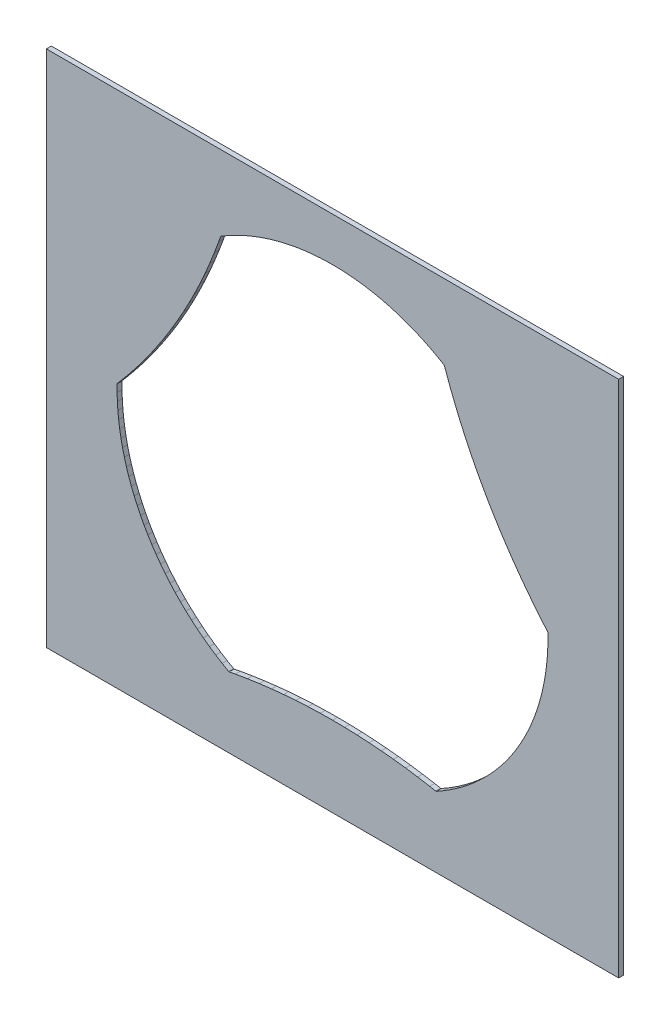
SolidWorks part; units mm, degrees
ref_plane "Front Plane" through (0, 0, 0) normal (0, 0, 1) x (1, 0, 0)
ref_plane "Top Plane" through (0, 0, 0) normal (0, 1, 0) x (1, 0, 0)
ref_plane "Right Plane" through (0, 0, 0) normal (1, 0, 0) x (0, 0, -1)
sketch "Model" plane through (0, 0, 0) normal (0, 0, 1) x (1, 0, 0)
  line L0 (125.677, -154.6098) -> (127.2049, -154.7174)
  line L1 (127.2049, -154.7174) -> (128.7281, -154.8785)
  line L2 (128.7281, -154.8785) -> (130.2447, -155.093)
  line L3 (130.2447, -155.093) -> (131.7528, -155.3606)
  line L4 (131.7528, -155.3606) -> (133.2506, -155.681)
  line L5 (133.2506, -155.681) -> (134.7362, -156.0539)
  line L6 (134.7362, -156.0539) -> (136.2078, -156.4787)
  line L7 (136.2078, -156.4787) -> (137.6636, -156.9549)
  line L8 (137.6636, -156.9549) -> (139.1018, -157.4819)
  line L9 (139.1018, -157.4819) -> (140.5205, -158.0591)
  line L10 (140.5205, -158.0591) -> (141.9181, -158.6858)
  line L11 (141.9181, -158.6858) -> (143.2929, -159.3612)
  line L12 (143.2929, -159.3612) -> (144.6431, -160.0844)
  line L13 (144.6431, -160.0844) -> (145.967, -160.8546)
  line L14 (145.967, -160.8546) -> (145.9831, -160.8702)
  line L15 (145.9831, -160.8702) -> (146.0021, -160.8822)
  line L16 (146.0021, -160.8822) -> (146.0122, -160.8983)
  line L17 (146.0122, -160.8983) -> (146.0259, -160.9116)
  line L18 (146.0259, -160.9116) -> (146.0336, -160.9326)
  line L19 (146.0336, -160.9326) -> (146.0455, -160.9517)
  line L20 (146.0455, -160.9517) -> (146.451, -162.1194)
  line L21 (146.451, -162.1194) -> (147.3137, -164.4362)
  line L22 (147.3137, -164.4362) -> (148.2279, -166.7332)
  line L23 (148.2279, -166.7332) -> (149.193, -169.0092)
  line L24 (149.193, -169.0092) -> (150.2086, -171.2632)
  line L25 (150.2086, -171.2632) -> (151.2742, -173.494)
  line L26 (151.2742, -173.494) -> (152.3892, -175.7006)
  line L27 (152.3892, -175.7006) -> (153.5531, -177.8817)
  line L28 (153.5531, -177.8817) -> (154.7653, -180.0363)
  line L29 (154.7653, -180.0363) -> (156.0251, -182.1634)
  line L30 (156.0251, -182.1634) -> (157.3321, -184.2619)
  line L31 (157.3321, -184.2619) -> (158.6855, -186.3308)
  line L32 (158.6855, -186.3308) -> (160.0847, -188.369)
  line L33 (160.0847, -188.369) -> (161.5289, -190.3755)
  line L34 (161.5289, -190.3755) -> (163.0174, -192.3494)
  line L35 (163.0174, -192.3494) -> (164.5496, -194.2896)
  line L36 (164.5496, -194.2896) -> (166.1246, -196.1952)
  line L37 (166.1246, -196.1952) -> (166.9332, -197.1302)
  line L38 (166.9332, -197.1302) -> (166.9437, -197.15)
  line L39 (166.9437, -197.15) -> (166.9581, -197.1673)
  line L40 (166.9581, -197.1673) -> (166.9627, -197.1857)
  line L41 (166.9627, -197.1857) -> (166.9716, -197.2025)
  line L42 (166.9716, -197.2025) -> (166.9725, -197.2249)
  line L43 (166.9725, -197.2249) -> (166.9779, -197.2467)
  line L44 (166.9779, -197.2467) -> (166.983, -198.7784)
  line L45 (166.983, -198.7784) -> (166.9343, -200.3093)
  line L46 (166.9343, -200.3093) -> (166.8318, -201.8375)
  line L47 (166.8318, -201.8375) -> (166.6757, -203.3612)
  line L48 (166.6757, -203.3612) -> (166.4662, -204.8785)
  line L49 (166.4662, -204.8785) -> (166.2036, -206.3875)
  line L50 (166.2036, -206.3875) -> (165.8881, -207.8864)
  line L51 (165.8881, -207.8864) -> (165.5201, -209.3732)
  line L52 (165.5201, -209.3732) -> (165.1002, -210.8462)
  line L53 (165.1002, -210.8462) -> (164.6288, -212.3036)
  line L54 (164.6288, -212.3036) -> (164.1065, -213.7435)
  line L55 (164.1065, -213.7435) -> (163.534, -215.1641)
  line L56 (163.534, -215.1641) -> (162.9119, -216.5638)
  line L57 (162.9119, -216.5638) -> (162.2411, -217.9408)
  line L58 (162.2411, -217.9408) -> (161.5223, -219.2933)
  line L59 (161.5223, -219.2933) -> (160.7565, -220.6198)
  line L60 (160.7565, -220.6198) -> (159.9445, -221.9186)
  line L61 (159.9445, -221.9186) -> (159.0874, -223.188)
  line L62 (159.0874, -223.188) -> (158.1863, -224.4266)
  line L63 (158.1863, -224.4266) -> (157.2423, -225.6327)
  line L64 (157.2423, -225.6327) -> (156.2564, -226.805)
  line L65 (156.2564, -226.805) -> (155.23, -227.9419)
  line L66 (155.23, -227.9419) -> (154.1643, -229.0421)
  line L67 (154.1643, -229.0421) -> (153.0607, -230.1041)
  line L68 (153.0607, -230.1041) -> (151.9204, -231.1268)
  line L69 (151.9204, -231.1268) -> (150.7449, -232.1087)
  line L70 (150.7449, -232.1087) -> (149.5356, -233.0488)
  line L71 (149.5356, -233.0488) -> (148.2941, -233.9458)
  line L72 (148.2941, -233.9458) -> (147.0218, -234.7987)
  line L73 (147.0218, -234.7987) -> (145.7204, -235.6064)
  line L74 (145.7204, -235.6064) -> (144.3914, -236.3678)
  line L75 (144.3914, -236.3678) -> (144.3698, -236.374)
  line L76 (144.3698, -236.374) -> (144.3499, -236.3845)
  line L77 (144.3499, -236.3845) -> (144.3309, -236.3851)
  line L78 (144.3309, -236.3851) -> (144.3126, -236.3903)
  line L79 (144.3126, -236.3903) -> (144.2905, -236.3865)
  line L80 (144.2905, -236.3865) -> (144.2681, -236.3873)
  line L81 (144.2681, -236.3873) -> (143.054, -236.1546)
  line L82 (143.054, -236.1546) -> (140.6163, -235.7434)
  line L83 (140.6163, -235.7434) -> (138.1699, -235.3866)
  line L84 (138.1699, -235.3866) -> (135.7162, -235.0844)
  line L85 (135.7162, -235.0844) -> (133.2564, -234.8369)
  line L86 (133.2564, -234.8369) -> (130.7917, -234.6443)
  line L87 (130.7917, -234.6443) -> (128.3233, -234.5067)
  line L88 (128.3233, -234.5067) -> (125.8525, -234.4241)
  line L89 (125.8525, -234.4241) -> (123.3804, -234.3965)
  line L90 (123.3804, -234.3965) -> (120.9083, -234.4241)
  line L91 (120.9083, -234.4241) -> (118.4375, -234.5067)
  line L92 (118.4375, -234.5067) -> (115.9691, -234.6443)
  line L93 (115.9691, -234.6443) -> (113.5044, -234.8369)
  line L94 (113.5044, -234.8369) -> (111.0446, -235.0844)
  line L95 (111.0446, -235.0844) -> (108.5909, -235.3866)
  line L96 (108.5909, -235.3866) -> (106.1445, -235.7434)
  line L97 (106.1445, -235.7434) -> (103.7067, -236.1546)
  line L98 (103.7067, -236.1546) -> (102.4927, -236.3873)
  line L99 (102.4927, -236.3873) -> (102.4703, -236.3865)
  line L100 (102.4703, -236.3865) -> (102.4482, -236.3903)
  line L101 (102.4482, -236.3903) -> (102.4299, -236.3851)
  line L102 (102.4299, -236.3851) -> (102.4109, -236.3845)
  line L103 (102.4109, -236.3845) -> (102.391, -236.374)
  line L104 (102.391, -236.374) -> (102.3694, -236.3678)
  line L105 (102.3694, -236.3678) -> (101.0404, -235.6064)
  line L106 (101.0404, -235.6064) -> (99.739, -234.7987)
  line L107 (99.739, -234.7987) -> (98.4667, -233.9458)
  line L108 (98.4667, -233.9458) -> (97.2252, -233.0488)
  line L109 (97.2252, -233.0488) -> (96.0159, -232.1087)
  line L110 (96.0159, -232.1087) -> (94.8404, -231.1268)
  line L111 (94.8404, -231.1268) -> (93.7001, -230.1041)
  line L112 (93.7001, -230.1041) -> (92.5965, -229.0421)
  line L113 (92.5965, -229.0421) -> (91.5308, -227.9419)
  line L114 (91.5308, -227.9419) -> (90.5044, -226.805)
  line L115 (90.5044, -226.805) -> (89.5185, -225.6327)
  line L116 (89.5185, -225.6327) -> (88.5745, -224.4266)
  line L117 (88.5745, -224.4266) -> (87.6733, -223.188)
  line L118 (87.6733, -223.188) -> (86.8163, -221.9186)
  line L119 (86.8163, -221.9186) -> (86.0043, -220.6198)
  line L120 (86.0043, -220.6198) -> (85.2385, -219.2933)
  line L121 (85.2385, -219.2933) -> (84.5197, -217.9408)
  line L122 (84.5197, -217.9408) -> (83.8488, -216.5638)
  line L123 (83.8488, -216.5638) -> (83.2268, -215.1641)
  line L124 (83.2268, -215.1641) -> (82.6542, -213.7435)
  line L125 (82.6542, -213.7435) -> (82.132, -212.3036)
  line L126 (82.132, -212.3036) -> (81.6606, -210.8462)
  line L127 (81.6606, -210.8462) -> (81.2406, -209.3732)
  line L128 (81.2406, -209.3732) -> (80.8727, -207.8864)
  line L129 (80.8727, -207.8864) -> (80.5572, -206.3875)
  line L130 (80.5572, -206.3875) -> (80.2946, -204.8785)
  line L131 (80.2946, -204.8785) -> (80.0851, -203.3612)
  line L132 (80.0851, -203.3612) -> (79.929, -201.8375)
  line L133 (79.929, -201.8375) -> (79.8265, -200.3093)
  line L134 (79.8265, -200.3093) -> (79.7778, -198.7784)
  line L135 (79.7778, -198.7784) -> (79.7828, -197.2467)
  line L136 (79.7828, -197.2467) -> (79.7883, -197.2249)
  line L137 (79.7883, -197.2249) -> (79.7892, -197.2025)
  line L138 (79.7892, -197.2025) -> (79.7981, -197.1857)
  line L139 (79.7981, -197.1857) -> (79.8027, -197.1672)
  line L140 (79.8027, -197.1672) -> (79.8171, -197.15)
  line L141 (79.8171, -197.15) -> (79.8276, -197.1302)
  line L142 (79.8276, -197.1302) -> (80.6361, -196.1952)
  line L143 (80.6361, -196.1952) -> (82.2112, -194.2896)
  line L144 (82.2112, -194.2896) -> (83.7433, -192.3494)
  line L145 (83.7433, -192.3494) -> (85.2319, -190.3755)
  line L146 (85.2319, -190.3755) -> (86.6761, -188.369)
  line L147 (86.6761, -188.369) -> (88.0753, -186.3308)
  line L148 (88.0753, -186.3308) -> (89.4287, -184.2619)
  line L149 (89.4287, -184.2619) -> (90.7356, -182.1634)
  line L150 (90.7356, -182.1634) -> (91.9955, -180.0363)
  line L151 (91.9955, -180.0363) -> (93.2077, -177.8817)
  line L152 (93.2077, -177.8817) -> (94.3716, -175.7005)
  line L153 (94.3716, -175.7005) -> (95.4866, -173.494)
  line L154 (95.4866, -173.494) -> (96.5521, -171.2632)
  line L155 (96.5521, -171.2632) -> (97.5677, -169.0092)
  line L156 (97.5677, -169.0092) -> (98.5329, -166.7332)
  line L157 (98.5329, -166.7332) -> (99.447, -164.4362)
  line L158 (99.447, -164.4362) -> (100.3098, -162.1194)
  line L159 (100.3098, -162.1194) -> (100.7153, -160.9517)
  line L160 (100.7153, -160.9517) -> (100.7272, -160.9326)
  line L161 (100.7272, -160.9326) -> (100.7349, -160.9116)
  line L162 (100.7349, -160.9116) -> (100.7486, -160.8983)
  line L163 (100.7486, -160.8983) -> (100.7587, -160.8822)
  line L164 (100.7587, -160.8822) -> (100.7776, -160.8702)
  line L165 (100.7776, -160.8702) -> (100.7938, -160.8546)
  line L166 (100.7938, -160.8546) -> (102.1177, -160.0844)
  line L167 (102.1177, -160.0844) -> (103.4679, -159.3612)
  line L168 (103.4679, -159.3612) -> (104.8426, -158.6858)
  line L169 (104.8426, -158.6858) -> (106.2403, -158.0591)
  line L170 (106.2403, -158.0591) -> (107.659, -157.4819)
  line L171 (107.659, -157.4819) -> (109.0972, -156.9549)
  line L172 (109.0972, -156.9549) -> (110.553, -156.4787)
  line L173 (110.553, -156.4787) -> (112.0246, -156.0539)
  line L174 (112.0246, -156.0539) -> (113.5102, -155.681)
  line L175 (113.5102, -155.681) -> (115.008, -155.3606)
  line L176 (115.008, -155.3606) -> (116.5161, -155.093)
  line L177 (116.5161, -155.093) -> (118.0327, -154.8785)
  line L178 (118.0327, -154.8785) -> (119.5559, -154.7174)
  line L179 (119.5559, -154.7174) -> (121.0838, -154.6098)
  line L180 (121.0838, -154.6098) -> (122.6145, -154.556)
  line L181 (122.6145, -154.556) -> (124.1462, -154.556)
  line L182 (124.1462, -154.556) -> (125.677, -154.6098)
  line L183 (79.7981, -197.1857) -> (166.9627, -197.1857) construction
  line L184 (144.3309, -236.3851) -> (100.7486, -160.8983) construction
  line L185 (146.0122, -160.8983) -> (102.4299, -236.3851) construction
  line L186 (123.3804, -197.1857) -> (123.3804, -200.0978) construction
  line L187 (122.5397, -198.6417) -> (125.0617, -197.1857) construction
  line L188 (124.221, -198.6417) -> (121.6991, -197.1857) construction
  point P190 (123.3804, -198.1564)
sketch "Sketch2" plane through (0, 0, 0) normal (0, 0, 1) x (1, 0, 0)
  line L1 (65.4557, -250.6328) -> (181.3051, -250.6328)
  line L2 (65.4557, -250.6328) -> (65.4557, -145.68)
  line L3 (65.4557, -145.68) -> (181.3051, -145.68)
  line L4 (181.3051, -250.6328) -> (181.3051, -145.68)
  line L5 (65.4557, -250.6328) -> (181.3051, -145.68) construction
  line L6 (65.4557, -145.68) -> (181.3051, -250.6328) construction
  point P0 (123.3804, -198.1564)
  dimension "D1" = 104.9528
  dimension "D2" = 115.8494
sketch "Sketch3" plane through (0, 0, 0) normal (0, 0, 1) x (1, 0, 0)
  line L0 (80.6361, -196.1952) -> (82.2112, -194.2896) construction
  line L1 (79.8276, -197.1302) -> (80.6361, -196.1952) construction
  line L2 (79.8171, -197.15) -> (79.8276, -197.1302) construction
  line L3 (79.8027, -197.1672) -> (79.8171, -197.15) construction
  line L4 (79.7981, -197.1857) -> (79.8027, -197.1672) construction
  line L5 (79.7892, -197.2025) -> (79.7981, -197.1857) construction
  line L6 (79.7883, -197.2249) -> (79.7892, -197.2025) construction
  line L7 (79.7828, -197.2467) -> (79.7883, -197.2249) construction
  line L8 (79.7778, -198.7784) -> (79.7828, -197.2467) construction
  line L9 (79.8265, -200.3093) -> (79.7778, -198.7784) construction
  line L10 (79.929, -201.8375) -> (79.8265, -200.3093) construction
  line L11 (80.0851, -203.3612) -> (79.929, -201.8375) construction
  line L12 (80.2946, -204.8785) -> (80.0851, -203.3612) construction
  line L13 (80.5572, -206.3875) -> (80.2946, -204.8785) construction
  line L14 (80.8727, -207.8864) -> (80.5572, -206.3875) construction
  line L15 (81.2406, -209.3732) -> (80.8727, -207.8864) construction
  line L16 (81.6606, -210.8462) -> (81.2406, -209.3732) construction
  line L17 (82.132, -212.3036) -> (81.6606, -210.8462) construction
  line L18 (82.6542, -213.7435) -> (82.132, -212.3036) construction
  line L19 (83.2268, -215.1641) -> (82.6542, -213.7435) construction
  line L20 (83.8488, -216.5638) -> (83.2268, -215.1641) construction
  line L21 (84.5197, -217.9408) -> (83.8488, -216.5638) construction
  line L22 (85.2385, -219.2933) -> (84.5197, -217.9408) construction
  line L23 (86.0043, -220.6198) -> (85.2385, -219.2933) construction
  line L24 (86.8163, -221.9186) -> (86.0043, -220.6198) construction
  line L25 (87.6733, -223.188) -> (86.8163, -221.9186) construction
  line L26 (88.5745, -224.4266) -> (87.6733, -223.188) construction
  line L27 (89.5185, -225.6327) -> (88.5745, -224.4266) construction
  line L28 (90.5044, -226.805) -> (89.5185, -225.6327) construction
  line L29 (91.5308, -227.9419) -> (90.5044, -226.805) construction
  line L30 (92.5965, -229.0421) -> (91.5308, -227.9419) construction
  line L31 (93.7001, -230.1041) -> (92.5965, -229.0421) construction
  line L32 (94.8404, -231.1268) -> (93.7001, -230.1041) construction
  line L33 (96.0159, -232.1087) -> (94.8404, -231.1268) construction
  line L34 (97.2252, -233.0488) -> (96.0159, -232.1087) construction
  line L35 (98.4667, -233.9458) -> (97.2252, -233.0488) construction
  line L36 (99.739, -234.7987) -> (98.4667, -233.9458) construction
  line L37 (101.0404, -235.6064) -> (99.739, -234.7987) construction
  line L38 (102.3694, -236.3678) -> (101.0404, -235.6064) construction
  line L39 (102.391, -236.374) -> (102.3694, -236.3678) construction
  line L40 (102.4109, -236.3845) -> (102.391, -236.374) construction
  line L41 (102.4299, -236.3851) -> (102.4109, -236.3845) construction
  line L42 (102.4482, -236.3903) -> (102.4299, -236.3851) construction
  line L43 (102.4703, -236.3865) -> (102.4482, -236.3903) construction
  line L44 (102.4927, -236.3873) -> (102.4703, -236.3865) construction
  line L45 (103.7067, -236.1546) -> (102.4927, -236.3873) construction
  line L46 (106.1445, -235.7434) -> (103.7067, -236.1546) construction
  line L47 (108.5909, -235.3866) -> (106.1445, -235.7434) construction
  line L48 (111.0446, -235.0844) -> (108.5909, -235.3866) construction
  line L49 (113.5044, -234.8369) -> (111.0446, -235.0844) construction
  line L50 (115.9691, -234.6443) -> (113.5044, -234.8369) construction
  line L51 (118.4375, -234.5067) -> (115.9691, -234.6443) construction
  line L52 (120.9083, -234.4241) -> (118.4375, -234.5067) construction
  line L53 (123.3804, -234.3965) -> (120.9083, -234.4241) construction
  line L54 (125.8525, -234.4241) -> (123.3804, -234.3965) construction
  line L55 (128.3233, -234.5067) -> (125.8525, -234.4241) construction
  line L56 (130.7917, -234.6443) -> (128.3233, -234.5067) construction
  line L57 (133.2564, -234.8369) -> (130.7917, -234.6443) construction
  line L58 (135.7162, -235.0844) -> (133.2564, -234.8369) construction
  line L59 (138.1699, -235.3866) -> (135.7162, -235.0844) construction
  line L60 (140.6163, -235.7434) -> (138.1699, -235.3866) construction
  line L61 (143.054, -236.1546) -> (140.6163, -235.7434) construction
  line L62 (144.2681, -236.3873) -> (143.054, -236.1546) construction
  line L63 (144.2905, -236.3865) -> (144.2681, -236.3873) construction
  line L64 (144.3126, -236.3903) -> (144.2905, -236.3865) construction
  line L65 (144.3309, -236.3851) -> (144.3126, -236.3903) construction
  line L66 (144.3499, -236.3845) -> (144.3309, -236.3851) construction
  line L67 (144.3698, -236.374) -> (144.3499, -236.3845) construction
  line L68 (144.3914, -236.3678) -> (144.3698, -236.374) construction
  line L69 (145.7204, -235.6064) -> (144.3914, -236.3678) construction
  line L70 (147.0218, -234.7987) -> (145.7204, -235.6064) construction
  line L71 (148.2941, -233.9458) -> (147.0218, -234.7987) construction
  line L72 (149.5356, -233.0488) -> (148.2941, -233.9458) construction
  line L73 (150.7449, -232.1087) -> (149.5356, -233.0488) construction
  line L74 (151.9204, -231.1268) -> (150.7449, -232.1087) construction
  line L75 (153.0607, -230.1041) -> (151.9204, -231.1268) construction
  line L76 (154.1643, -229.0421) -> (153.0607, -230.1041) construction
  line L77 (155.23, -227.9419) -> (154.1643, -229.0421) construction
  line L78 (156.2564, -226.805) -> (155.23, -227.9419) construction
  line L79 (157.2423, -225.6327) -> (156.2564, -226.805) construction
  line L80 (158.1863, -224.4266) -> (157.2423, -225.6327) construction
  line L81 (159.0874, -223.188) -> (158.1863, -224.4266) construction
  line L82 (159.9445, -221.9186) -> (159.0874, -223.188) construction
  line L83 (160.7565, -220.6198) -> (159.9445, -221.9186) construction
  line L84 (161.5223, -219.2933) -> (160.7565, -220.6198) construction
  line L85 (162.2411, -217.9408) -> (161.5223, -219.2933) construction
  line L86 (162.9119, -216.5638) -> (162.2411, -217.9408) construction
  line L87 (163.534, -215.1641) -> (162.9119, -216.5638) construction
  line L88 (164.1065, -213.7435) -> (163.534, -215.1641) construction
  line L89 (164.6288, -212.3036) -> (164.1065, -213.7435) construction
  line L90 (165.1002, -210.8462) -> (164.6288, -212.3036) construction
  line L91 (165.5201, -209.3732) -> (165.1002, -210.8462) construction
  line L92 (165.8881, -207.8864) -> (165.5201, -209.3732) construction
  line L93 (166.2036, -206.3875) -> (165.8881, -207.8864) construction
  line L94 (166.4662, -204.8785) -> (166.2036, -206.3875) construction
  line L95 (166.6757, -203.3612) -> (166.4662, -204.8785) construction
  line L96 (166.8318, -201.8375) -> (166.6757, -203.3612) construction
  line L97 (166.9343, -200.3093) -> (166.8318, -201.8375) construction
  line L98 (166.983, -198.7784) -> (166.9343, -200.3093) construction
  line L99 (166.9779, -197.2467) -> (166.983, -198.7784) construction
  line L100 (166.9725, -197.2249) -> (166.9779, -197.2467) construction
  line L101 (166.9716, -197.2025) -> (166.9725, -197.2249) construction
  line L102 (166.9627, -197.1857) -> (166.9716, -197.2025) construction
  line L103 (166.9581, -197.1673) -> (166.9627, -197.1857) construction
  line L104 (166.9437, -197.15) -> (166.9581, -197.1673) construction
  line L105 (166.9332, -197.1302) -> (166.9437, -197.15) construction
  line L106 (166.1246, -196.1952) -> (166.9332, -197.1302) construction
  line L107 (164.5496, -194.2896) -> (166.1246, -196.1952) construction
  line L108 (163.0174, -192.3494) -> (164.5496, -194.2896) construction
  line L109 (161.5289, -190.3755) -> (163.0174, -192.3494) construction
  line L110 (160.0847, -188.369) -> (161.5289, -190.3755) construction
  line L111 (158.6855, -186.3308) -> (160.0847, -188.369) construction
  line L112 (157.3321, -184.2619) -> (158.6855, -186.3308) construction
  line L113 (156.0251, -182.1634) -> (157.3321, -184.2619) construction
  line L114 (154.7653, -180.0363) -> (156.0251, -182.1634) construction
  line L115 (153.5531, -177.8817) -> (154.7653, -180.0363) construction
  line L116 (152.3892, -175.7006) -> (153.5531, -177.8817) construction
  line L117 (151.2742, -173.494) -> (152.3892, -175.7006) construction
  line L118 (150.2086, -171.2632) -> (151.2742, -173.494) construction
  line L119 (149.193, -169.0092) -> (150.2086, -171.2632) construction
  line L120 (148.2279, -166.7332) -> (149.193, -169.0092) construction
  line L121 (147.3137, -164.4362) -> (148.2279, -166.7332) construction
  line L122 (146.451, -162.1194) -> (147.3137, -164.4362) construction
  line L123 (146.0455, -160.9517) -> (146.451, -162.1194) construction
  line L124 (146.0336, -160.9326) -> (146.0455, -160.9517) construction
  line L125 (146.0259, -160.9116) -> (146.0336, -160.9326) construction
  line L126 (146.0122, -160.8983) -> (146.0259, -160.9116) construction
  line L127 (146.0021, -160.8822) -> (146.0122, -160.8983) construction
  line L128 (145.9831, -160.8702) -> (146.0021, -160.8822) construction
  line L129 (145.967, -160.8546) -> (145.9831, -160.8702) construction
  line L130 (144.6431, -160.0844) -> (145.967, -160.8546) construction
  line L131 (143.2929, -159.3612) -> (144.6431, -160.0844) construction
  line L132 (141.9181, -158.6858) -> (143.2929, -159.3612) construction
  line L133 (140.5205, -158.0591) -> (141.9181, -158.6858) construction
  line L134 (139.1018, -157.4819) -> (140.5205, -158.0591) construction
  line L135 (137.6636, -156.9549) -> (139.1018, -157.4819) construction
  line L136 (136.2078, -156.4787) -> (137.6636, -156.9549) construction
  line L137 (134.7362, -156.0539) -> (136.2078, -156.4787) construction
  line L138 (133.2506, -155.681) -> (134.7362, -156.0539) construction
  line L139 (131.7528, -155.3606) -> (133.2506, -155.681) construction
  line L140 (130.2447, -155.093) -> (131.7528, -155.3606) construction
  line L141 (128.7281, -154.8785) -> (130.2447, -155.093) construction
  line L142 (127.2049, -154.7174) -> (128.7281, -154.8785) construction
  line L143 (125.677, -154.6098) -> (127.2049, -154.7174) construction
  line L144 (124.1462, -154.556) -> (125.677, -154.6098) construction
  line L145 (122.6145, -154.556) -> (124.1462, -154.556) construction
  line L146 (121.0838, -154.6098) -> (122.6145, -154.556) construction
  line L147 (119.5559, -154.7174) -> (121.0838, -154.6098) construction
  line L148 (118.0327, -154.8785) -> (119.5559, -154.7174) construction
  line L149 (116.5161, -155.093) -> (118.0327, -154.8785) construction
  line L150 (115.008, -155.3606) -> (116.5161, -155.093) construction
  line L151 (113.5102, -155.681) -> (115.008, -155.3606) construction
  line L152 (112.0246, -156.0539) -> (113.5102, -155.681) construction
  line L153 (110.553, -156.4787) -> (112.0246, -156.0539) construction
  line L154 (109.0972, -156.9549) -> (110.553, -156.4787) construction
  line L155 (107.659, -157.4819) -> (109.0972, -156.9549) construction
  line L156 (106.2403, -158.0591) -> (107.659, -157.4819) construction
  line L157 (104.8426, -158.6858) -> (106.2403, -158.0591) construction
  line L158 (103.4679, -159.3612) -> (104.8426, -158.6858) construction
  line L159 (102.1177, -160.0844) -> (103.4679, -159.3612) construction
  line L160 (100.7938, -160.8546) -> (102.1177, -160.0844) construction
  line L161 (100.7776, -160.8702) -> (100.7938, -160.8546) construction
  line L162 (100.7587, -160.8822) -> (100.7776, -160.8702) construction
  line L163 (100.7486, -160.8983) -> (100.7587, -160.8822) construction
  line L164 (100.7349, -160.9116) -> (100.7486, -160.8983) construction
  line L165 (100.7272, -160.9326) -> (100.7349, -160.9116) construction
  line L166 (100.7153, -160.9517) -> (100.7272, -160.9326) construction
  line L167 (100.3098, -162.1194) -> (100.7153, -160.9517) construction
  line L168 (99.447, -164.4362) -> (100.3098, -162.1194) construction
  line L169 (98.5329, -166.7332) -> (99.447, -164.4362) construction
  line L170 (97.5677, -169.0092) -> (98.5329, -166.7332) construction
  line L171 (96.5521, -171.2632) -> (97.5677, -169.0092) construction
  line L172 (95.4866, -173.494) -> (96.5521, -171.2632) construction
  line L173 (94.3716, -175.7005) -> (95.4866, -173.494) construction
  line L174 (93.2077, -177.8817) -> (94.3716, -175.7005) construction
  line L175 (91.9955, -180.0363) -> (93.2077, -177.8817) construction
  line L176 (90.7356, -182.1634) -> (91.9955, -180.0363) construction
  line L177 (89.4287, -184.2619) -> (90.7356, -182.1634) construction
  line L178 (88.0753, -186.3308) -> (89.4287, -184.2619) construction
  line L179 (86.6761, -188.369) -> (88.0753, -186.3308) construction
  line L180 (85.2319, -190.3755) -> (86.6761, -188.369) construction
  line L181 (83.7433, -192.3494) -> (85.2319, -190.3755) construction
  line L182 (82.2112, -194.2896) -> (83.7433, -192.3494) construction
  line L183 (80.6361, -196.1952) -> (82.2112, -194.2896)
  line L184 (79.8276, -197.1302) -> (80.6361, -196.1952)
  line L185 (79.8171, -197.15) -> (79.8276, -197.1302)
  line L186 (79.8027, -197.1672) -> (79.8171, -197.15)
  line L187 (79.7981, -197.1857) -> (79.8027, -197.1672)
  line L188 (79.7892, -197.2025) -> (79.7981, -197.1857)
  line L189 (79.7883, -197.2249) -> (79.7892, -197.2025)
  line L190 (79.7828, -197.2467) -> (79.7883, -197.2249)
  line L191 (79.7778, -198.7784) -> (79.7828, -197.2467)
  line L192 (79.8265, -200.3093) -> (79.7778, -198.7784)
  line L193 (79.929, -201.8375) -> (79.8265, -200.3093)
  line L194 (80.0851, -203.3612) -> (79.929, -201.8375)
  line L195 (80.2946, -204.8785) -> (80.0851, -203.3612)
  line L196 (80.5572, -206.3875) -> (80.2946, -204.8785)
  line L197 (80.8727, -207.8864) -> (80.5572, -206.3875)
  line L198 (81.2406, -209.3732) -> (80.8727, -207.8864)
  line L199 (81.6606, -210.8462) -> (81.2406, -209.3732)
  line L200 (82.132, -212.3036) -> (81.6606, -210.8462)
  line L201 (82.6542, -213.7435) -> (82.132, -212.3036)
  line L202 (83.2268, -215.1641) -> (82.6542, -213.7435)
  line L203 (83.8488, -216.5638) -> (83.2268, -215.1641)
  line L204 (84.5197, -217.9408) -> (83.8488, -216.5638)
  line L205 (85.2385, -219.2933) -> (84.5197, -217.9408)
  line L206 (86.0043, -220.6198) -> (85.2385, -219.2933)
  line L207 (86.8163, -221.9186) -> (86.0043, -220.6198)
  line L208 (87.6733, -223.188) -> (86.8163, -221.9186)
  line L209 (88.5745, -224.4266) -> (87.6733, -223.188)
  line L210 (89.5185, -225.6327) -> (88.5745, -224.4266)
  line L211 (90.5044, -226.805) -> (89.5185, -225.6327)
  line L212 (91.5308, -227.9419) -> (90.5044, -226.805)
  line L213 (92.5965, -229.0421) -> (91.5308, -227.9419)
  line L214 (93.7001, -230.1041) -> (92.5965, -229.0421)
  line L215 (94.8404, -231.1268) -> (93.7001, -230.1041)
  line L216 (96.0159, -232.1087) -> (94.8404, -231.1268)
  line L217 (97.2252, -233.0488) -> (96.0159, -232.1087)
  line L218 (98.4667, -233.9458) -> (97.2252, -233.0488)
  line L219 (99.739, -234.7987) -> (98.4667, -233.9458)
  line L220 (101.0404, -235.6064) -> (99.739, -234.7987)
  line L221 (102.3694, -236.3678) -> (101.0404, -235.6064)
  line L222 (102.391, -236.374) -> (102.3694, -236.3678)
  line L223 (102.4109, -236.3845) -> (102.391, -236.374)
  line L224 (102.4299, -236.3851) -> (102.4109, -236.3845)
  line L225 (102.4482, -236.3903) -> (102.4299, -236.3851)
  line L226 (102.4703, -236.3865) -> (102.4482, -236.3903)
  line L227 (102.4927, -236.3873) -> (102.4703, -236.3865)
  line L228 (103.7067, -236.1546) -> (102.4927, -236.3873)
  line L229 (106.1445, -235.7434) -> (103.7067, -236.1546)
  line L230 (108.5909, -235.3866) -> (106.1445, -235.7434)
  line L231 (111.0446, -235.0844) -> (108.5909, -235.3866)
  line L232 (113.5044, -234.8369) -> (111.0446, -235.0844)
  line L233 (115.9691, -234.6443) -> (113.5044, -234.8369)
  line L234 (118.4375, -234.5067) -> (115.9691, -234.6443)
  line L235 (120.9083, -234.4241) -> (118.4375, -234.5067)
  line L236 (123.3804, -234.3965) -> (120.9083, -234.4241)
  line L237 (125.8525, -234.4241) -> (123.3804, -234.3965)
  line L238 (128.3233, -234.5067) -> (125.8525, -234.4241)
  line L239 (130.7917, -234.6443) -> (128.3233, -234.5067)
  line L240 (133.2564, -234.8369) -> (130.7917, -234.6443)
  line L241 (135.7162, -235.0844) -> (133.2564, -234.8369)
  line L242 (138.1699, -235.3866) -> (135.7162, -235.0844)
  line L243 (140.6163, -235.7434) -> (138.1699, -235.3866)
  line L244 (143.054, -236.1546) -> (140.6163, -235.7434)
  line L245 (144.2681, -236.3873) -> (143.054, -236.1546)
  line L246 (144.2905, -236.3865) -> (144.2681, -236.3873)
  line L247 (144.3126, -236.3903) -> (144.2905, -236.3865)
  line L248 (144.3309, -236.3851) -> (144.3126, -236.3903)
  line L249 (144.3499, -236.3845) -> (144.3309, -236.3851)
  line L250 (144.3698, -236.374) -> (144.3499, -236.3845)
  line L251 (144.3914, -236.3678) -> (144.3698, -236.374)
  line L252 (145.7204, -235.6064) -> (144.3914, -236.3678)
  line L253 (147.0218, -234.7987) -> (145.7204, -235.6064)
  line L254 (148.2941, -233.9458) -> (147.0218, -234.7987)
  line L255 (149.5356, -233.0488) -> (148.2941, -233.9458)
  line L256 (150.7449, -232.1087) -> (149.5356, -233.0488)
  line L257 (151.9204, -231.1268) -> (150.7449, -232.1087)
  line L258 (153.0607, -230.1041) -> (151.9204, -231.1268)
  line L259 (154.1643, -229.0421) -> (153.0607, -230.1041)
  line L260 (155.23, -227.9419) -> (154.1643, -229.0421)
  line L261 (156.2564, -226.805) -> (155.23, -227.9419)
  line L262 (157.2423, -225.6327) -> (156.2564, -226.805)
  line L263 (158.1863, -224.4266) -> (157.2423, -225.6327)
  line L264 (159.0874, -223.188) -> (158.1863, -224.4266)
  line L265 (159.9445, -221.9186) -> (159.0874, -223.188)
  line L266 (160.7565, -220.6198) -> (159.9445, -221.9186)
  line L267 (161.5223, -219.2933) -> (160.7565, -220.6198)
  line L268 (162.2411, -217.9408) -> (161.5223, -219.2933)
  line L269 (162.9119, -216.5638) -> (162.2411, -217.9408)
  line L270 (163.534, -215.1641) -> (162.9119, -216.5638)
  line L271 (164.1065, -213.7435) -> (163.534, -215.1641)
  line L272 (164.6288, -212.3036) -> (164.1065, -213.7435)
  line L273 (165.1002, -210.8462) -> (164.6288, -212.3036)
  line L274 (165.5201, -209.3732) -> (165.1002, -210.8462)
  line L275 (165.8881, -207.8864) -> (165.5201, -209.3732)
  line L276 (166.2036, -206.3875) -> (165.8881, -207.8864)
  line L277 (166.4662, -204.8785) -> (166.2036, -206.3875)
  line L278 (166.6757, -203.3612) -> (166.4662, -204.8785)
  line L279 (166.8318, -201.8375) -> (166.6757, -203.3612)
  line L280 (166.9343, -200.3093) -> (166.8318, -201.8375)
  line L281 (166.983, -198.7784) -> (166.9343, -200.3093)
  line L282 (166.9779, -197.2467) -> (166.983, -198.7784)
  line L283 (166.9725, -197.2249) -> (166.9779, -197.2467)
  line L284 (166.9716, -197.2025) -> (166.9725, -197.2249)
  line L285 (166.9627, -197.1857) -> (166.9716, -197.2025)
  line L286 (166.9581, -197.1673) -> (166.9627, -197.1857)
  line L287 (166.9437, -197.15) -> (166.9581, -197.1673)
  line L288 (166.9332, -197.1302) -> (166.9437, -197.15)
  line L289 (166.1246, -196.1952) -> (166.9332, -197.1302)
  line L290 (164.5496, -194.2896) -> (166.1246, -196.1952)
  line L291 (163.0174, -192.3494) -> (164.5496, -194.2896)
  line L292 (161.5289, -190.3755) -> (163.0174, -192.3494)
  line L293 (160.0847, -188.369) -> (161.5289, -190.3755)
  line L294 (158.6855, -186.3308) -> (160.0847, -188.369)
  line L295 (157.3321, -184.2619) -> (158.6855, -186.3308)
  line L296 (156.0251, -182.1634) -> (157.3321, -184.2619)
  line L297 (154.7653, -180.0363) -> (156.0251, -182.1634)
  line L298 (153.5531, -177.8817) -> (154.7653, -180.0363)
  line L299 (152.3892, -175.7006) -> (153.5531, -177.8817)
  line L300 (151.2742, -173.494) -> (152.3892, -175.7006)
  line L301 (150.2086, -171.2632) -> (151.2742, -173.494)
  line L302 (149.193, -169.0092) -> (150.2086, -171.2632)
  line L303 (148.2279, -166.7332) -> (149.193, -169.0092)
  line L304 (147.3137, -164.4362) -> (148.2279, -166.7332)
  line L305 (146.451, -162.1194) -> (147.3137, -164.4362)
  line L306 (146.0455, -160.9517) -> (146.451, -162.1194)
  line L307 (146.0336, -160.9326) -> (146.0455, -160.9517)
  line L308 (146.0259, -160.9116) -> (146.0336, -160.9326)
  line L309 (146.0122, -160.8983) -> (146.0259, -160.9116)
  line L310 (146.0021, -160.8822) -> (146.0122, -160.8983)
  line L311 (145.9831, -160.8702) -> (146.0021, -160.8822)
  line L312 (145.967, -160.8546) -> (145.9831, -160.8702)
  line L313 (144.6431, -160.0844) -> (145.967, -160.8546)
  line L314 (143.2929, -159.3612) -> (144.6431, -160.0844)
  line L315 (141.9181, -158.6858) -> (143.2929, -159.3612)
  line L316 (140.5205, -158.0591) -> (141.9181, -158.6858)
  line L317 (139.1018, -157.4819) -> (140.5205, -158.0591)
  line L318 (137.6636, -156.9549) -> (139.1018, -157.4819)
  line L319 (136.2078, -156.4787) -> (137.6636, -156.9549)
  line L320 (134.7362, -156.0539) -> (136.2078, -156.4787)
  line L321 (133.2506, -155.681) -> (134.7362, -156.0539)
  line L322 (131.7528, -155.3606) -> (133.2506, -155.681)
  line L323 (130.2447, -155.093) -> (131.7528, -155.3606)
  line L324 (128.7281, -154.8785) -> (130.2447, -155.093)
  line L325 (127.2049, -154.7174) -> (128.7281, -154.8785)
  line L326 (125.677, -154.6098) -> (127.2049, -154.7174)
  line L327 (124.1462, -154.556) -> (125.677, -154.6098)
  line L328 (122.6145, -154.556) -> (124.1462, -154.556)
  line L329 (121.0838, -154.6098) -> (122.6145, -154.556)
  line L330 (119.5559, -154.7174) -> (121.0838, -154.6098)
  line L331 (118.0327, -154.8785) -> (119.5559, -154.7174)
  line L332 (116.5161, -155.093) -> (118.0327, -154.8785)
  line L333 (115.008, -155.3606) -> (116.5161, -155.093)
  line L334 (113.5102, -155.681) -> (115.008, -155.3606)
  line L335 (112.0246, -156.0539) -> (113.5102, -155.681)
  line L336 (110.553, -156.4787) -> (112.0246, -156.0539)
  line L337 (109.0972, -156.9549) -> (110.553, -156.4787)
  line L338 (107.659, -157.4819) -> (109.0972, -156.9549)
  line L339 (106.2403, -158.0591) -> (107.659, -157.4819)
  line L340 (104.8426, -158.6858) -> (106.2403, -158.0591)
  line L341 (103.4679, -159.3612) -> (104.8426, -158.6858)
  line L342 (102.1177, -160.0844) -> (103.4679, -159.3612)
  line L343 (100.7938, -160.8546) -> (102.1177, -160.0844)
  line L344 (100.7776, -160.8702) -> (100.7938, -160.8546)
  line L345 (100.7587, -160.8822) -> (100.7776, -160.8702)
  line L346 (100.7486, -160.8983) -> (100.7587, -160.8822)
  line L347 (100.7349, -160.9116) -> (100.7486, -160.8983)
  line L348 (100.7272, -160.9326) -> (100.7349, -160.9116)
  line L349 (100.7153, -160.9517) -> (100.7272, -160.9326)
  line L350 (100.3098, -162.1194) -> (100.7153, -160.9517)
  line L351 (99.447, -164.4362) -> (100.3098, -162.1194)
  line L352 (98.5329, -166.7332) -> (99.447, -164.4362)
  line L353 (97.5677, -169.0092) -> (98.5329, -166.7332)
  line L354 (96.5521, -171.2632) -> (97.5677, -169.0092)
  line L355 (95.4866, -173.494) -> (96.5521, -171.2632)
  line L356 (94.3716, -175.7005) -> (95.4866, -173.494)
  line L357 (93.2077, -177.8817) -> (94.3716, -175.7005)
  line L358 (91.9955, -180.0363) -> (93.2077, -177.8817)
  line L359 (90.7356, -182.1634) -> (91.9955, -180.0363)
  line L360 (89.4287, -184.2619) -> (90.7356, -182.1634)
  line L361 (88.0753, -186.3308) -> (89.4287, -184.2619)
  line L362 (86.6761, -188.369) -> (88.0753, -186.3308)
  line L363 (85.2319, -190.3755) -> (86.6761, -188.369)
  line L364 (83.7433, -192.3494) -> (85.2319, -190.3755)
  line L365 (82.2112, -194.2896) -> (83.7433, -192.3494)
extrude "Boss-Extrude1" add sketch "Sketch2" along normal blind 1
extrude "Cut-Extrude2" cut sketch "Sketch3" along normal through all
